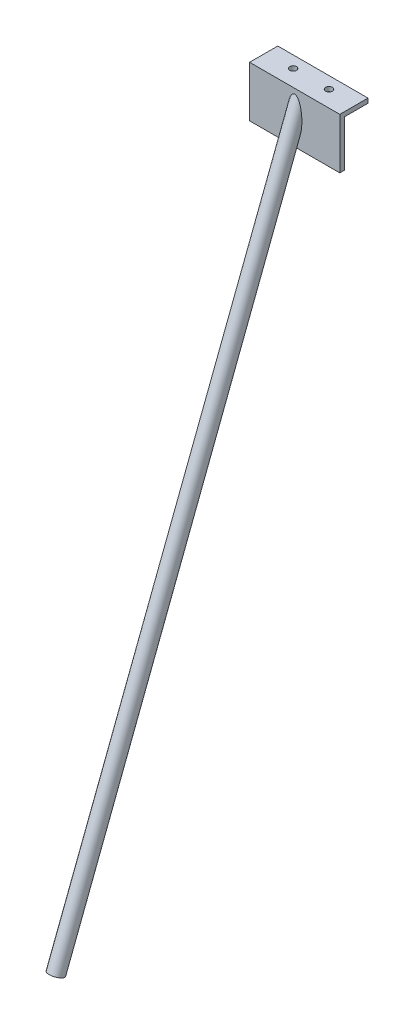
SolidWorks part; units mm, degrees
ref_plane "Front Plane" through (0, 0, 0) normal (0, 0, 1) x (1, 0, 0)
ref_plane "Top Plane" through (0, 0, 0) normal (0, 1, 0) x (1, 0, 0)
ref_plane "Right Plane" through (0, 0, 0) normal (1, 0, 0) x (0, 0, -1)
sketch "Sketch1" plane through (0, 0, 0) normal (1, 0, 0) x (0, 0, -1)
  line L0 (0, 0) -> (25, 0)
  line L1 (25, 0) -> (25, -4)
  line L2 (25, -4) -> (4, -4)
  line L3 (4, -4) -> (4, -45)
  line L4 (4, -45) -> (0, -45)
  line L5 (0, -45) -> (0, 0)
  dimension "D1" = 25
  dimension "D2" = 4
  dimension "D3" = 45
  dimension "D4" = 4
extrude "Boss-Extrude1" add sketch "Sketch1" along normal blind 80
ref_plane "Plane1" through (0, -39.2208, 15.0554) normal (0, 0.9336, -0.3584) x (-1, 0, 0)
sketch "Sketch2" plane through (0, -39.2208, 15.0554) normal (0, 0.9336, -0.3584) x (-1, 0, 0)
  line L0 (-80, -16.1266) -> (0, -16.1266) construction
  circle A0 centre (-40, -8) radius 6.375
  circle A1 centre (-40, -8) radius 4.9
  point P3 (0, 0)
  point P4 (0, 0)
  point P8 (-40, -16.1266)
  dimension "D1" = 12.75
  dimension "D2" = 9.8
extrude "Boss-Extrude2" add sketch "Sketch2" along normal up to surface and the other way blind 570 up to face at (40, -22.5, 0)
hole_wizard "Ø6.0mm Dowel Hole1" positions "Sketch3" profile "Sketch4" hole size "Ø6.0" standard "ISO" end condition through all
sketch "Sketch3" plane through (0, 0, 0) normal (0, 1, 0) x (1, 0, 0)
  line L1 (80, 25) -> (0, 25) construction
  line L4 (24.055, 14.5) -> (55.945, 14.5) construction
  point P0 (24.055, 14.5)
  point P2 (55.945, 14.5)
  point P23 (40, 14.5)
  point P24 (40, 25)
  dimension "D1" = 10.5
  dimension "D3" = 31.89
sketch "Sketch4" plane through (24.055, 0, -14.5) normal (1, 0, 0) x (0, 0, 1)
  line L0 (0, 0) -> (0, 576.5131)
  line L1 (0, 576.5131) -> (3, 576.5131)
  line L2 (3, 576.5131) -> (3, 0)
  line L5 (3, 0) -> (0, 0)
  line L11 (0, -6.35) -> (0, 107.95) construction
  dimension "Thru Hole Dia." = 6
  dimension "Thru Hole Depth" = 576.5131
equation "\"D4@Sketch1\"=\"D2@Sketch1\""
